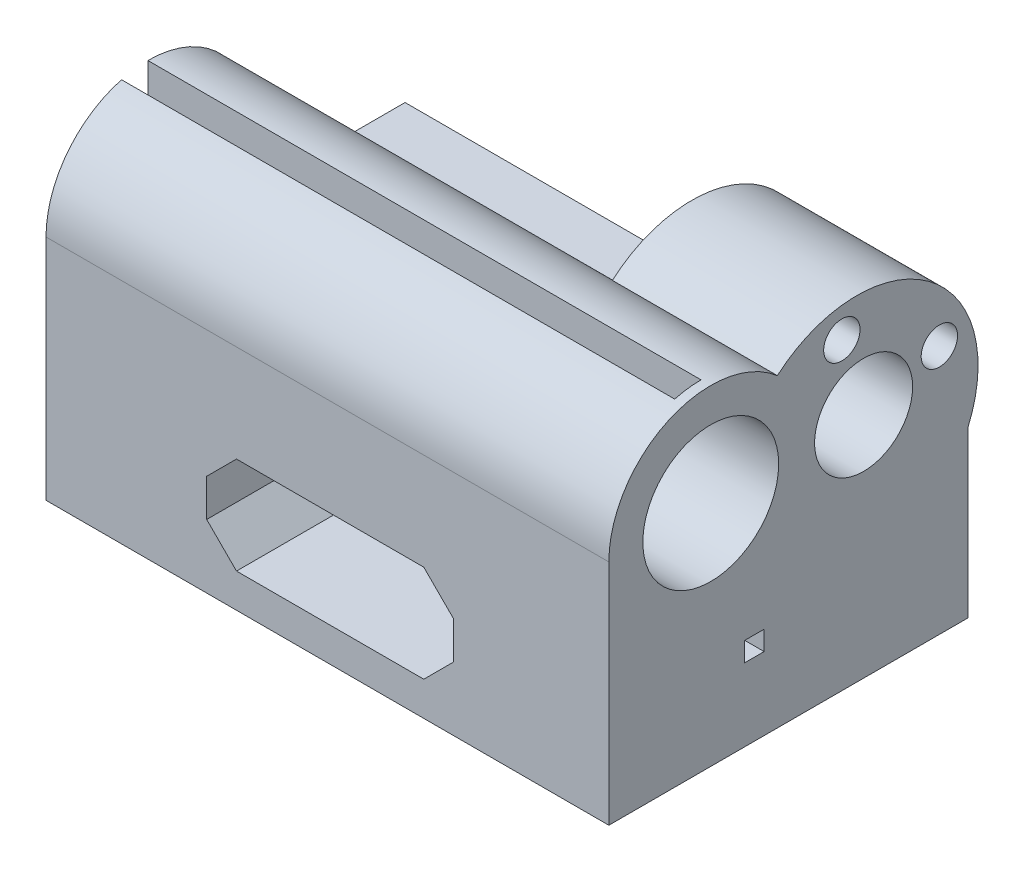
SolidWorks part; units mm, degrees
ref_plane "Front Plane" through (0, 0, 0) normal (0, 0, 1) x (1, 0, 0)
ref_plane "Top Plane" through (0, 0, 0) normal (0, 1, 0) x (1, 0, 0)
ref_plane "Right Plane" through (0, 0, 0) normal (1, 0, 0) x (0, 0, -1)
sketch "Sketch2" plane through (0, 0, 0) normal (0, 1, 0) x (1, 0, 0)
  line L1 (-29, -18.5) -> (29, -18.5)
  line L2 (-29, -18.5) -> (-29, 18.5)
  line L3 (-29, 18.5) -> (29, 18.5)
  line L4 (29, -18.5) -> (29, 18.5)
  line L5 (-29, -18.5) -> (29, 18.5) construction
  line L6 (-29, 18.5) -> (29, -18.5) construction
  point P0 (0, 0)
  dimension "D1" = 58
  dimension "D2" = 37
extrude "Boss-Extrude1" add sketch "Sketch2" along normal blind 17
sketch "Sketch3" plane through (29, 0, 0) normal (1, 0, 0) x (0, 0, -1)
  line L0 (-18.5, 0) -> (18.5, 0) construction
  line L1 (-18.5, 23.5) -> (-18.5, 17)
  line L2 (-18.5, 17) -> (-18.5, 0) construction
  line L5 (2.5, 23.5) -> (2.5, 17)
  line L6 (-18.5, 17) -> (18.5, 17) construction
  line L7 (-18.5, 17) -> (2.5, 17)
  arc A0 (2.5, 23.5) -> (-18.5, 23.5) centre (-8, 23.5) ccw
  dimension "D2" = 21
  dimension "D4" = 23.5
  dimension "D5" = 10.5
extrude "Boss-Extrude2" add sketch "Sketch3" against normal up to surface (58 mm away) up to face at (-29, 8.5, 0)
sketch "Sketch4" plane through (29, 0, 0) normal (1, 0, 0) x (0, 0, -1)
  line L1 (-18.5, 0) -> (18.5, 0) construction
  circle A0 centre (7.0436, 22) radius 12.5
  dimension "D1" = 25
  dimension "D2" = 22
extrude "Boss-Extrude3" add sketch "Sketch4" against normal blind 17
sketch "Sketch5" plane through (0, 0, -18.5) normal (0, 0, -1) x (-1, 0, 0)
  line L0 (-13, 6.57) -> (-13, 10.427)
  line L1 (-13, 10.427) -> (-9.93, 13.497)
  line L2 (-9.93, 13.497) -> (9.37, 13.497)
  line L3 (9.37, 13.497) -> (12.44, 10.427)
  line L4 (12.44, 10.427) -> (12.44, 6.57)
  line L5 (12.44, 6.57) -> (9.37, 3.5)
  line L6 (9.37, 3.5) -> (-9.93, 3.5)
  line L7 (-9.93, 3.5) -> (-13, 6.57)
  line L8 (-29, 0) -> (29, 0) construction
  line L9 (-29, 17) -> (-29, 0) construction
  dimension "D1" = 3.857
  dimension "D2" = 3.857
  dimension "D3" = 135
  dimension "D4" = 135
  dimension "D5" = 3.07
  dimension "D6" = 3.07
  dimension "D7" = 3.07
  dimension "D8" = 3.07
  dimension "D9" = 19.3
  dimension "D10" = 3.5
  dimension "D11" = 16
extrude "Cut-Extrude1" cut sketch "Sketch5" against normal through all
sketch "Sketch6" plane through (0, 0, -18.5) normal (0, 0, -1) x (-1, 0, 0)
  line L0 (-29, 0) -> (29, 0) construction
  line L1 (-29, 17) -> (-29, 0) construction
  circle A0 centre (-23, 8.5) radius 4.076
  circle A1 centre (22, 8.5) radius 4.076
  dimension "D5" = 8.152
  dimension "D6" = 8.152
  dimension "D1" = 8.5
  dimension "D2" = 8.5
  dimension "D3" = 6
  dimension "D4" = 51
extrude "Cut-Extrude2" cut sketch "Sketch6" against normal blind 23
sketch "Sketch7" plane through (29, 0, 0) normal (1, 0, 0) x (0, 0, -1)
  line L0 (-18.5, 23.5) -> (-18.5, 0) construction
  line L1 (-18.5, 0) -> (18.5, 0) construction
  circle A0 centre (-8, 23.5) radius 7
  circle A1 centre (7.7501, 23.5) radius 5.05
  dimension "D1" = 10.1
  dimension "D2" = 14
  dimension "D3" = 26.2501
  dimension "D4" = 23.5
extrude "Cut-Extrude3" cut sketch "Sketch7" against normal through all
sketch "Sketch8" plane through (29, 0, 0) normal (1, 0, 0) x (0, 0, -1)
  line L0 (7.7501, 23.5) -> (5.5097, 31.31) construction
  line L3 (7.7501, 23.5) -> (15.5601, 25.7405) construction
  line L4 (5.5097, 31.31) -> (6.0267, 29.5077) construction
  line L7 (15.5601, 25.7405) -> (13.7578, 25.2235) construction
  circle A1 centre (5.5097, 31.31) radius 1.875
  circle A2 centre (15.5601, 25.7405) radius 1.875
  dimension "D1" = 3.75
  dimension "D2" = 6.25
  dimension "D3" = 3.75
  dimension "D7" = 6.25
extrude "Cut-Extrude4" cut sketch "Sketch8" against normal through all
sketch "Sketch12" plane through (-29, 0, 0) normal (-1, 0, 0) x (0, 0, 1)
  line L0 (-18.5, 17) -> (-18.5, 0) construction
  line L1 (4.5, 7.5) -> (2.5, 7.5)
  line L2 (4.5, 7.5) -> (4.5, 9.5)
  line L3 (4.5, 9.5) -> (2.5, 9.5)
  line L4 (2.5, 7.5) -> (2.5, 9.5)
  line L5 (-18.5, 0) -> (18.5, 0) construction
  dimension "D1" = 23
  dimension "D2" = 2
  dimension "D3" = 2
  dimension "D4" = 7.5
extrude "Cut-Extrude6" cut sketch "Sketch12" against normal blind 8
mirror "Mirror1" about plane through (0, 0, 0) normal (1, 0, 0) of "Cut-Extrude6"
sketch "Sketch13" plane through (-29, 0, 0) normal (-1, 0, 0) x (0, 0, 1)
  line L0 (8, 23.5) -> (10.7176, 33.6422) construction
  line L1 (8, 23.5) -> (-2.5, 23.5) construction
  line L2 (8, 23.5) -> (8, 34) construction
  line L3 (9.8117, 30.2615) -> (10.7176, 33.6422)
  line L4 (8, 34) -> (8, 30.5)
  arc A0 (9.8117, 30.2615) -> (8, 30.5) centre (8, 23.5) ccw
  arc A1 (-2.5, 23.5) -> (8, 34) centre (8, 23.5) ccw
  arc A2 (18.5, 23.5) -> (-2.5, 23.5) centre (8, 23.5) ccw construction
  arc A3 (1.1397, 31.449) -> (-2.5, 23.5) centre (8, 23.5) ccw construction
  circle A4 centre (8, 23.5) radius 7 construction
  point P7 (17.5768, 27.8053)
  point P11 (0.5754, 30.9246)
  point P15 (-2.7001, 23.5)
  circle M5 centre (8, 23.5) radius 7
  arc M8 (18.5, 23.5) -> (-2.5, 23.5) centre (8, 23.5) ccw
  dimension "D1" = 15
  dimension "D2" = 90
extrude "Cut-Extrude7" cut sketch "Sketch13" against normal blind 57 contours L4 L3 M8 M5 region at (-29, 32.2657, 9.154)
